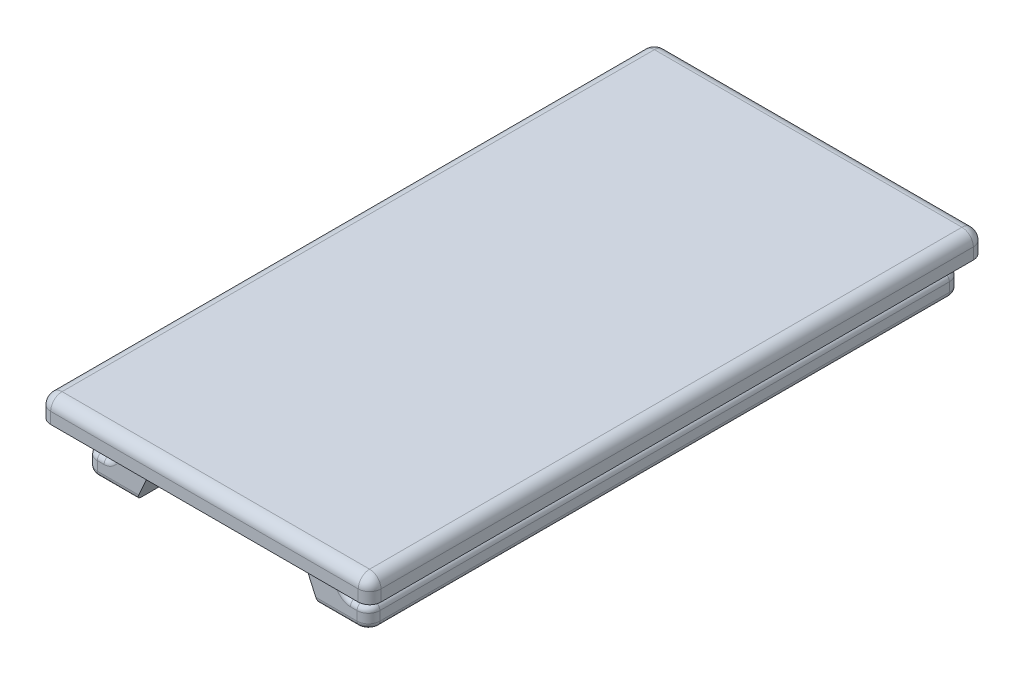
SolidWorks part; units mm, degrees
ref_plane "Front Plane" through (0, 0, 0) normal (0, 0, 1) x (1, 0, 0)
ref_plane "Top Plane" through (0, 0, 0) normal (0, 1, 0) x (1, 0, 0)
ref_plane "Right Plane" through (0, 0, 0) normal (1, 0, 0) x (0, 0, -1)
sketch "Sketch1" plane through (0, 0, 0) normal (0, 1, 0) x (1, 0, 0)
  line L1 (-14.5, -27) -> (14.5, -27)
  line L2 (-14.5, -27) -> (-14.5, 27)
  line L3 (-14.5, 27) -> (14.5, 27)
  line L4 (14.5, -27) -> (14.5, 27)
  line L5 (-14.5, -27) -> (14.5, 27) construction
  line L6 (-14.5, 27) -> (14.5, -27) construction
  point P0 (0, 0)
  dimension "D1" = 29
  dimension "D2" = 54
extrude "Boss-Extrude1" add sketch "Sketch1" along normal blind 2
sketch "Sketch2" plane through (0, 0, -27) normal (0, 0, -1) x (-1, 0, 0)
  line L0 (-14.5, 0) -> (14.5, 0) construction
  line L1 (-14.5, 0) -> (14.5, 0) construction
  line L2 (-10.4, 0) -> (-10.4, -2.2)
  line L3 (-10.4, -2.2) -> (-12.4, -2.2)
  line L4 (-12.4, -2.2) -> (-12.4, -4)
  line L5 (-12.4, -4) -> (-8, -4)
  line L6 (-8, -4) -> (-8, 0)
  line L7 (-8, 0) -> (-10.4, 0)
  line L8 (0, 0) -> (0, -12.6777) construction
  line L10 (-14.5, 2) -> (-14.5, 0) construction
  dimension "D1" = 4.1
  dimension "D2" = 1.8
  dimension "D3" = 2.2
  dimension "D4" = 2
  dimension "D5" = 8
extrude "Boss-Extrude2" add sketch "Sketch2" against normal blind 52
mirror "Mirror1" about plane through (0, 0, 0) normal (1, 0, 0) of "Boss-Extrude2"
sketch "Sketch4" plane through (0, 0, -27) normal (0, 0, -1) x (-1, 0, 0)
  line L0 (8, -4) -> (8, 0) construction
  line L1 (-8, 0) -> (8, 0) construction
  line L2 (-8, -4) -> (-8, 0) construction
  line L3 (8, -4) -> (8, 0)
  line L4 (-8, 0) -> (8, 0)
  line L5 (-8, -4) -> (-8, 0)
  line L6 (-8, -4) -> (8, -4)
extrude "Boss-Extrude3" add sketch "Sketch4" against normal blind 3
chamfer "Chamfer1" distance 4 distance2 1.8 1 edges at (-8, 0, 0.5) first distance on face at (-8, -2, 0.5)
chamfer "Chamfer2" distance 1.8 distance2 4 1 edges at (8, 0, 0.5) first distance on face at (0.3, 0, -0.1667)
fillet "Fillet1" radius 1 16 edges at (0, 2, 27) (-14.5, 2, 0) (0, 2, -27) (14.5, 2, 0) (-12.4, -3.1, -27) (12.4, -3.1, -27) (-12.4, -3.1, 25) (12.4, -3.1, 25) (10.4, -1.1, 25) (-10.4, -1.1, 25) (10.4, -1.1, -27) (-10.4, -1.1, -27) (14.5, 1, 27) (14.5, 1, -27) (-14.5, 1, -27) (-14.5, 1, 27)
fillet "Fillet3" radius 0.5 33 edges at (-7.8, 0, 25) (-10.1071, 0, 24.7071) (-10.1071, 0, -26.7071) (7.8, 0, 25) (10.1071, 0, 24.7071) (10.1071, 0, -26.7071) (10.4, -2.2, 25) (12.1071, -2.2, 24.7071) (10.4, -2.2, -27) (12.1071, -2.2, -26.7071) (10.1071, -2.2, 24.7071) (10.1071, -2.2, -26.7071) (-9.7, -4, 25) (-12.1071, -4, 24.7071) (9.7, -4, 25) (12.1071, -4, 24.7071) (12.4, -4, -1) (12.1071, -4, -26.7071) (0, -4, -27) (-12.1071, -4, -26.7071) (-10.4, -2.2, 25) (-12.1071, -2.2, 24.7071) (-10.4, -2.2, -27) (-12.1071, -2.2, -26.7071) (-10.1071, -2.2, 24.7071) (-10.1071, -2.2, -26.7071) (-10.4, 0, -1) (10.4, 0, -1) (12.4, -2.2, -1) (10.4, -2.2, -1) (-12.4, -4, -1) (-12.4, -2.2, -1) (-10.4, -2.2, -1)
sketch "Sketch3" plane through (0, 0, 0) normal (0, -1, 0) x (1, 0, 0)
  line L0 (0, 0) -> (0, 20.2627) construction
  line L1 (-1, 16) -> (-2.5, 16)
  line L2 (-1, 8) -> (1, 8)
  line L3 (-1, 8) -> (-1, 16)
  line L5 (1, 8) -> (1, 16)
  line L6 (-1, 8) -> (1, 16) construction
  line L7 (-1, 16) -> (1, 8) construction
  line L8 (-2.5, 16) -> (0, 18.5)
  line L9 (1, 16) -> (2.5, 16)
  line L10 (2.5, 16) -> (0, 18.5)
  point P3 (0, 12)
  dimension "D1" = 8
  dimension "D2" = 2
  dimension "D3" = 8
  dimension "D4" = 1.5
  dimension "D5" = 45
extrude "Cut-Extrude1" cut sketch "Sketch3" against normal blind 0.3 contours L5 L9 L10 L8 L1 L3 L2
